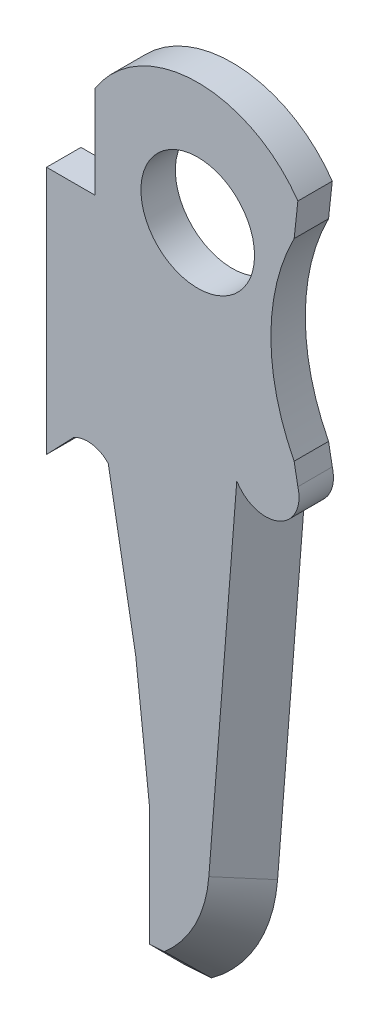
SolidWorks part; units mm, degrees
material "Plain Carbon Steel"
ref_plane "Front Plane" through (0, 0, 0) normal (0, 0, 1) x (1, 0, 0)
ref_plane "Top Plane" through (0, 0, 0) normal (0, 1, 0) x (1, 0, 0)
ref_plane "Right Plane" through (0, 0, 0) normal (1, 0, 0) x (0, 0, -1)
sketch "Sketch1" plane through (0, 0, 0) normal (0, 0, 1) x (1, 0, 0)
  line L0 (15.0593, 33.8835) -> (75.2966, 33.8835) construction
  line L1 (41.3063, 38.244) -> (41.3063, 29.0678)
  line L2 (41.3063, 29.0678) -> (42.3113, 30.116)
  line L3 (41.3063, 38.244) -> (43.0843, 38.244)
  line L4 (43.0843, 38.244) -> (43.0843, 41.6401)
  line L5 (43.5813, 29.9178) -> (44.5973, 24.274)
  line L6 (44.5973, 24.274) -> (45.1053, 19.702)
  line L7 (45.1053, 19.702) -> (45.1053, 14.0476)
  line L8 (49.5506, 31.132) -> (48.5597, 18.4742)
  line L9 (46.1213, 14.114) -> (45.1053, 14.0476)
  line L10 (50.5773, 32.6721) -> (50.4393, 33.418)
  line L11 (50.5773, 41.8) -> (50.4393, 40.53)
  arc A1 (46.1213, 14.114) -> (48.5597, 18.4742) centre (42.6092, 18.94) ccw
  arc A2 (43.5813, 29.9178) -> (42.3113, 30.116) centre (42.8193, 29.203) ccw
  arc A3 (50.5773, 41.8) -> (43.0843, 41.6401) centre (46.8833, 39.26) ccw
  arc A4 (50.4393, 40.53) -> (50.4393, 33.418) centre (57.3759, 36.974) ccw
  arc A5 (49.5506, 31.132) -> (50.5773, 32.6721) centre (49.3902, 32.3512) ccw
  point P11 (0, 0)
  dimension "D3" = 4.483
  dimension "D4" = 1.0448
  dimension "D5" = 7.795
  dimension "D6" = 1.2297
  dimension "D7" = 5.9686
  dimension "D25" = 20.32
  dimension "D1" = 9.271
  dimension "D2" = 1.778
  dimension "D8" = 9.1762
  dimension "D9" = 15.0202
  dimension "D10" = 2.54
  dimension "D11" = 1.27
  dimension "D12" = 2.286
  dimension "D13" = 3.556
  dimension "D14" = 1.016
  dimension "D15" = 9.144
  dimension "D16" = 4.572
  dimension "D17" = 4.064
  dimension "D18" = 14.986
  dimension "D19" = 2.286
  dimension "D20" = 3.302
  dimension "D21" = 19.558
  dimension "D22" = 1.778
  dimension "D23" = 25.146
  dimension "D24" = 0.762
  dimension "D26" = 8.128
  dimension "D27" = 1.6764
  dimension "D28" = 6.9088
  dimension "D29" = 3.556
extrude "Boss-Extrude1" add sketch "Sketch1" along normal blind 1.27
sketch "Sketch2" plane through (0, 0, 1.27) normal (0, 0, 1) x (1, 0, 0)
  circle A0 centre (46.8833, 39.26) radius 2.0955
  dimension "D1" = 4.191
extrude "Cut-Extrude1" cut sketch "Sketch2" against normal through all
chamfer "Chamfer1" distance 1.27 angle 45 3 edges at (45.6133, 14.0808, 1.27) (47.8186, 16.0267, 1.27) (49.0551, 24.8031, 1.27)
